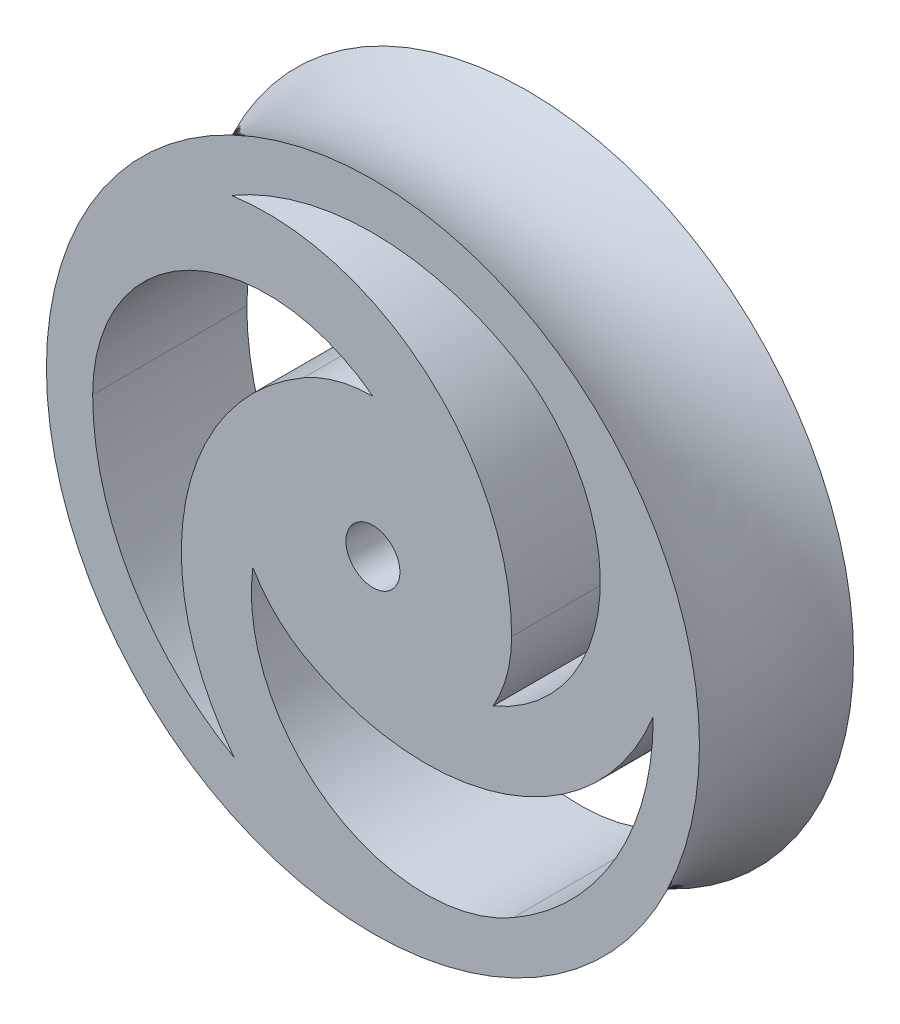
SolidWorks part; units mm, degrees
ref_plane "Front Plane" through (0, 0, 0) normal (0, 0, 1) x (1, 0, 0)
ref_plane "Top Plane" through (0, 0, 0) normal (0, 1, 0) x (1, 0, 0)
ref_plane "Right Plane" through (0, 0, 0) normal (1, 0, 0) x (0, 0, -1)
sketch "Sketch2" plane through (0, 0, 0) normal (0, 1, 0) x (1, 0, 0)
  line L0 (0, 5) -> (0, -5)
  line L1 (0, 5) -> (21.1839, 5)
  line L2 (0, -5) -> (21.1839, -5)
  line L3 (0, 0) -> (20, 0) construction
  arc A0 (21.1839, 5) -> (21.1839, -5) centre (31.15, 0) ccw
  point P4 (0, 0)
  point P11 (20, 0)
  dimension "D3" = 11.15
  dimension "D1" = 10
  dimension "D2" = 20
revolve "Revolve1" add sketch "Sketch2" angle 360 about L0
sketch "Sketch3" plane through (0, 0, -5) normal (0, 0, -1) x (-1, 0, 0)
  line L0 (0, 0) -> (0, 21.1839) construction
  line L1 (0, 0) -> (18.1839, 0) construction
  circle A0 centre (0, 0) radius 1.75
  circle A1 centre (0, 0) radius 18.1839 construction
  circle A2 centre (0, 0) radius 21.1839 construction
  arc A3 (-9, 0) -> (9.1839, 15.6943) centre (6.8647, 0) cw construction
  arc A4 (0, 9) -> (18.1839, 0) centre (6.8647, 0) cw construction
  arc A5 (9.1839, 15.6943) -> (18.1839, 0) centre (0, 0) cw construction
  circle A6 centre (0, 0) radius 9 construction
  arc A7 (-9, 0) -> (0, 9) centre (0, 0) cw construction
  arc A8 (7.7942, -4.5) -> (-9.092, -15.7477) centre (-3.4324, -5.945) cw construction
  arc A9 (4.5, 7.7942) -> (7.7942, -4.5) centre (0, 0) cw construction
  arc A10 (4.5, 7.7942) -> (8.9997, -15.8007) centre (-3.4324, -5.945) cw construction
  arc A11 (8.9997, -15.8007) -> (-9.092, -15.7477) centre (0, 0) cw construction
  arc A12 (-7.7942, -4.5) -> (-9.092, 15.7477) centre (-3.4324, 5.945) cw construction
  arc A13 (4.5, -7.7942) -> (-7.7942, -4.5) centre (0, 0) cw construction
  arc A14 (4.5, -7.7942) -> (-18.1836, 0.1064) centre (-3.4324, 5.945) cw construction
  arc A15 (-18.1836, 0.1064) -> (-9.092, 15.7477) centre (0, 0) cw construction
  arc A16 (0, 9) -> (18.1839, 0) centre (6.8647, 0) cw
  arc A17 (18.1839, 0) -> (8.9997, -15.8007) centre (0, 0) cw
  arc A18 (4.5, 7.7942) -> (8.9997, -15.8007) centre (-3.4324, -5.945) cw
  arc A19 (0, 9) -> (4.5, 7.7942) centre (0, 0) cw
  arc A20 (7.7942, -4.5) -> (4.5, -7.7942) centre (0, 0) cw
  arc A21 (7.7942, -4.5) -> (-9.092, -15.7477) centre (-3.4324, -5.945) cw
  arc A22 (-9.092, -15.7477) -> (-18.1836, 0.1064) centre (0, 0) cw
  arc A23 (4.5, -7.7942) -> (-18.1836, 0.1064) centre (-3.4324, 5.945) cw
  arc A24 (-7.7942, -4.5) -> (-9, 0) centre (0, 0) cw
  arc A25 (-7.7942, -4.5) -> (-9.092, 15.7477) centre (-3.4324, 5.945) cw
  arc A26 (-9.092, 15.7477) -> (9.1839, 15.6943) centre (0, 0) cw
  arc A27 (-9, 0) -> (9.1839, 15.6943) centre (6.8647, 0) cw
  circle A28 centre (0, 0) radius 21.1839 construction
  point P26 (0, 0)
  point P45 (0, 0)
  point P48 (0, 0)
  dimension "D1" = 3.5
  dimension "D2" = 18
  dimension "D5" = 3
  dimension "D3" = 3
  dimension "D4" = 3
extrude "Cut-Extrude1" cut sketch "Sketch3" against normal through all
sketch "Sketch4" plane through (0, 0, -5) normal (0, 0, -1) x (-1, 0, 0)
  circle A0 centre (0, 0) radius 9
  circle A1 centre (0, 0) radius 1.75
  dimension "D1" = 18
extrude "Boss-Extrude1" add sketch "Sketch4" along normal blind 8
sketch "Sketch5" plane through (0, 0, 0) normal (1, 0, 0) x (0, 0, -1)
  line L0 (5, 0) -> (13, 0) construction
  line L1 (5, -21.1839) -> (5, 21.1839) construction
  line L2 (13, -9) -> (13, 9) construction
  circle A0 centre (9, 0) radius 1.65
  point P9 (9.353, -1.5282)
  point P10 (9, 0)
  dimension "D1" = 3.3
extrude "Cut-Extrude2" cut sketch "Sketch5" against normal through all
ref_plane "Plane1" through (-2.7, 0, 0) normal (1, 0, 0) x (0, 0, -1)
sketch "Sketch6" plane through (-2.7, 0, 0) normal (1, 0, 0) x (0, 0, -1)
  line L0 (10.6454, 2.85) -> (13, 2.85)
  line L1 (7.3546, -2.85) -> (10.6454, -2.85)
  line L2 (10.6454, -2.85) -> (12.2909, 0) construction
  line L3 (12.2909, 0) -> (10.6454, 2.85) construction
  line L4 (10.6454, 2.85) -> (7.3546, 2.85)
  line L5 (7.3546, 2.85) -> (5.7091, 0)
  line L6 (5.7091, 0) -> (7.3546, -2.85)
  line L7 (13, -9) -> (13, 9) construction
  line L8 (13, 2.85) -> (13, -2.85)
  line L9 (13, -2.85) -> (10.6454, -2.85)
  circle A0 centre (9, 0) radius 2.85 construction
  dimension "D1" = 5.7
extrude "Cut-Extrude3" cut sketch "Sketch6" against normal blind 2.7
